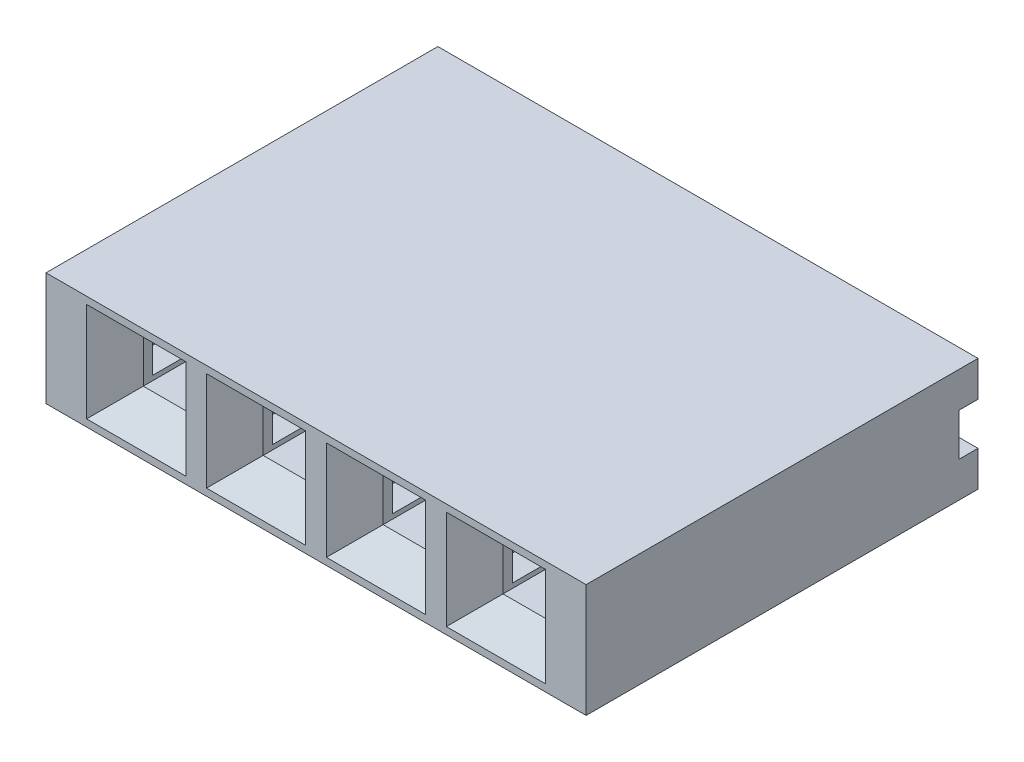
SolidWorks part; units mm, degrees
note: The reader was unsure of these and kept them because the rebuilt part matched: shared geometry of "Эскиз-БоковаяНакладка<2>".
other "Пластик"
ref_plane "Front Plane" through (0, 0, 0) normal (0, 0, 1) x (1, 0, 0)
ref_plane "Top Plane" through (0, 0, 0) normal (0, 1, 0) x (1, 0, 0)
ref_plane "Right Plane" through (0, 0, 0) normal (1, 0, 0) x (0, 0, -1)
sketch "Эскиз-ВнутреннееСечение" plane through (0, 0, 0) normal (0, 0, 1) x (1, 0, 0)
  line L0 (-1, 0.35) -> (-0.45, 0.35)
  line L1 (-1.27, -1.2) -> (1.27, -1.2)
  line L2 (-1.27, -1.2) -> (-1.27, 1.2)
  line L3 (-1.27, 1.2) -> (1.27, 1.2)
  line L4 (1.27, -1.2) -> (1.27, 1.2)
  line L5 (-1.27, -1.2) -> (1.27, 1.2) construction
  line L6 (-1.27, 1.2) -> (1.27, -1.2) construction
  line L8 (-1, -0.35) -> (-1, 0.35)
  line L9 (-0.45, 0.45) -> (0.45, 0.45)
  line L11 (0, 1.2) -> (0, -1.2) construction
  line L12 (0.45, 0.35) -> (0.45, 0.45)
  line L13 (-1.27, 0) -> (1.27, 0) construction
  line L14 (1, 0.35) -> (0.45, 0.35)
  line L15 (-0.45, 0.35) -> (-0.45, 0.45)
  line L16 (1, -0.35) -> (0.45, -0.35)
  line L17 (0.45, -0.35) -> (0.45, -0.45)
  line L18 (-0.45, -0.35) -> (-0.45, -0.45)
  line L19 (-1, -0.35) -> (-0.45, -0.35)
  line L20 (-0.45, -0.45) -> (0.45, -0.45)
  line L21 (1, -0.35) -> (1, 0.35)
  point P0 (0, 0)
  point P5 (0, 0)
  dimension "D1" = 2.4
  dimension "D2" = 2.54
  dimension "D3" = 1
  dimension "D4" = 0.35
  dimension "D5" = 0.1
  dimension "D7" = 0.55
extrude "Бобышка-ОтЦентраВверхВниз" add sketch "Эскиз-ВнутреннееСечение" against normal blind 0.4 and the other way blind 6.7 contours L8 L0 L15 L9 L12 L14 L21 L16 L17 L20 L18 L19
sketch "Эскиз-СамыйНиз" plane through (0, 0, -0.4) normal (0, 0, -1) x (-1, 0, 0)
  line L1 (1.27, 1.2) -> (1.27, -1.2) construction
  line L2 (-1.27, -1.2) -> (-1.27, 1.2) construction
  line L3 (0.45, -0.45) -> (-0.45, -0.45) construction
  line L4 (1.27, -1.2) -> (-1.27, -1.2)
  line L5 (1.27, -1.2) -> (1.27, -0.45)
  line L6 (1.27, -0.45) -> (-1.27, -0.45)
  line L7 (-1.27, -1.2) -> (-1.27, -0.45)
  line L9 (-1.27, 1.2) -> (1.27, 1.2)
  line L10 (-1.27, 1.2) -> (-1.27, 0.45)
  line L11 (-1.27, 0.45) -> (1.27, 0.45)
  line L12 (1.27, 1.2) -> (1.27, 0.45)
  line L13 (-0.45, 0.45) -> (0.45, 0.45) construction
extrude "Бобышка-СамыйНиз" add sketch "Эскиз-СамыйНиз" along normal blind 0.4
sketch "Эскиз-ВерхняяПеремычка" plane through (0, 0, 6.7) normal (0, 0, 1) x (1, 0, 0)
  line L1 (-1.27, 1.2) -> (1.27, 1.2)
  line L2 (-1.27, 1.2) -> (-1.27, -1.2)
  line L3 (-1.27, -1.2) -> (1.27, -1.2)
  line L4 (1.27, 1.2) -> (1.27, -1.2)
  line L5 (-0.45, -0.45) -> (0.45, -0.45)
  line L6 (-0.45, -0.45) -> (-0.45, 0.45)
  line L7 (-0.45, 0.45) -> (0.45, 0.45)
  line L8 (0.45, -0.45) -> (0.45, 0.45)
  line L9 (-0.45, -0.45) -> (0.45, 0.45) construction
  line L10 (-0.45, 0.45) -> (0.45, -0.45) construction
  point P4 (0, 0)
extrude "Бобышка-СамыйВерх" add sketch "Эскиз-ВерхняяПеремычка" along normal blind 0.8
chamfer "Фаска-СверхуВнутрь" distance 0.6 angle 45 4 edges at (0, -0.45, 7.5) (0.45, 0, 7.5) (0, 0.45, 7.5) (-0.45, 0, 7.5)
pattern_linear "Пластик_Массив" count 4 spacing 2.54 along (-1, 0, 0) of bodies 103
combine bodies "Соединить_Массив" operation type add bodies to combine 103 106 105 104
sketch "Эскиз-БоковаяНакладка" plane through (1.27, 0, 0) normal (1, 0, 0) x (0, 0, -1)
  line L1 (0.8, 1.2) -> (0.8, 0.45)
  line L2 (0.8, 0.45) -> (0.4, 0.45)
  line L3 (0.4, 0.45) -> (0.4, -0.45)
  line L4 (0.4, -0.45) -> (0.4, 0.45) construction
  line L5 (0.4, -0.45) -> (0.8, -0.45)
  line L6 (0.8, -0.45) -> (0.8, -1.2)
  line L7 (0.8, -1.2) -> (-7.5, -1.2)
  line L8 (-7.5, -1.2) -> (-7.5, 1.2)
  line L9 (-7.5, 1.2) -> (0.8, 1.2)
extrude "Бобышка-БоковаяНакладка1" add sketch "Эскиз-БоковаяНакладка" along normal blind 0.64 from surface at 0 starting at face at (1.27, 0, 1.375)
extrude "Бобышка-БоковаяНакладка2" add sketch "Эскиз-БоковаяНакладка<2>" against normal blind 0.64 from surface
sketch "Эскиз-БоковаяНакладка<2>" plane through (1.27, 0, 0) normal (1, 0, 0) x (0, 0, -1) same geometry as "Эскиз-БоковаяНакладка"
